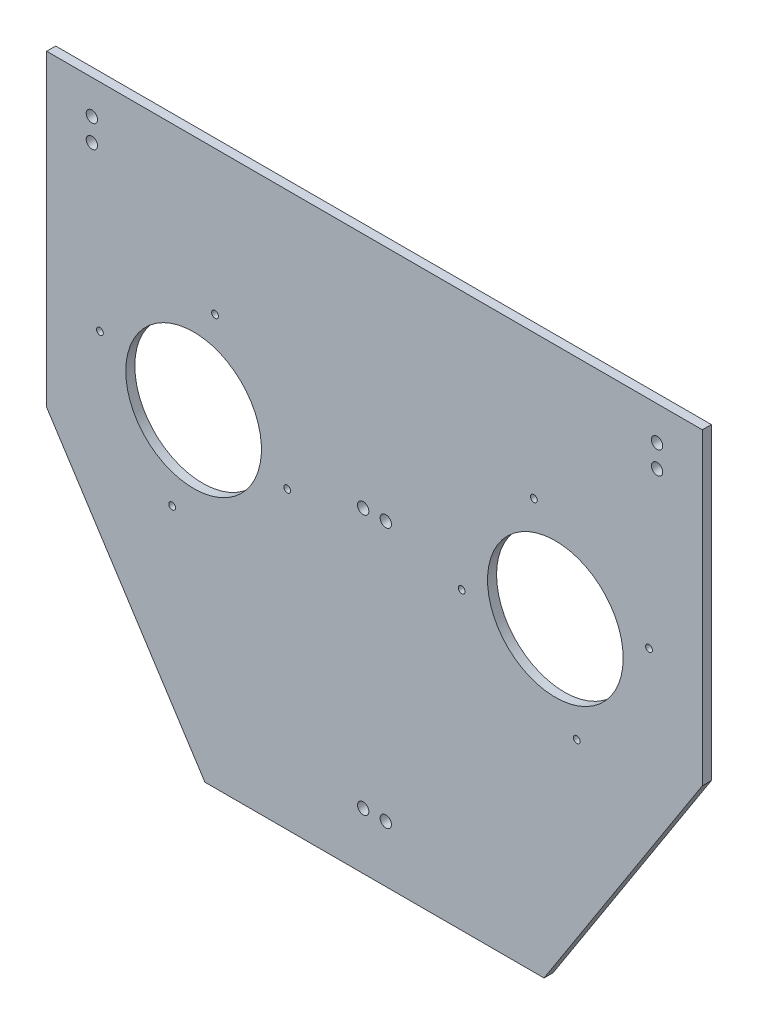
SolidWorks part; units mm, degrees
ref_plane "Front Plane" through (0, 0, 0) normal (0, 0, 1) x (1, 0, 0)
ref_plane "Top Plane" through (0, 0, 0) normal (0, 1, 0) x (1, 0, 0)
ref_plane "Right Plane" through (0, 0, 0) normal (1, 0, 0) x (0, 0, -1)
sketch "Sketch1" plane through (0, 0, 0) normal (0, 0, 1) x (1, 0, 0)
  line L0 (-125, 100) -> (125, 100) construction
  line L1 (-125, 0) -> (125, 0) construction
  line L2 (-145, -16.3871) -> (-75, -125)
  line L3 (-75, -125) -> (75, -125)
  line L4 (75, -125) -> (145, -16.3871)
  line L5 (-125, 105) -> (-125, 95) construction
  line L6 (0, -125) -> (0, 100) construction
  line L7 (-145, 120) -> (145, 120)
  line L8 (145, 120) -> (145, -16.3871)
  line L11 (-145, -16.3871) -> (-145, 120)
  line L12 (125, 105) -> (125, 95) construction
  line L13 (-5, -100) -> (5, -100) construction
  circle A0 centre (-125, 100) radius 12.5 construction
  circle A10 centre (-125, 0) radius 12.5 construction
  circle A11 centre (125, 0) radius 12.5 construction
  circle A12 centre (-125, 0) radius 17.5 construction
  circle A13 centre (-125, 100) radius 17.5 construction
  circle A25 centre (-125, 95) radius 2.5
  circle A26 centre (-125, 105) radius 2.5
  circle A27 centre (125, 95) radius 2.5
  circle A28 centre (125, 105) radius 2.5
  circle A29 centre (5, -100) radius 2.5
  circle A30 centre (-5, -100) radius 2.5
  point P12 (0, 100)
  point P15 (0, -100)
  point P45 (0, 120)
  dimension "D1" = 25
  dimension "D2" = 5
  dimension "D4" = 100
  dimension "D6" = 5
  dimension "D11" = 20
  dimension "D12" = 20
  dimension "D7" = 10
  dimension "D8" = 250
  dimension "D3" = 25
  dimension "D5" = 100
  dimension "D9" = 150
extrude "Boss-Extrude1" add sketch "Sketch1" along normal blind 4
sketch "Sketch2" plane through (0, 0, 4) normal (0, 0, 1) x (1, 0, 0)
  line L0 (121.4264, 24.4924) -> (38.5736, 5.5076) construction
  line L1 (89.4924, -26.4264) -> (70.5076, 56.4264) construction
  line L2 (0, 0) -> (0, 96.4486) construction
  line L3 (145, 120) -> (-145, 120) construction
  line L4 (-145, 120) -> (-145, -16.3871) construction
  line L5 (-80, 15) -> (80, 15) construction
  line L6 (-5, 15) -> (5, 15) construction
  circle A0 centre (80, 15) radius 42.5 construction
  circle A1 centre (38.5736, 5.5076) radius 1.5
  circle A2 centre (70.5076, 56.4264) radius 1.5
  circle A3 centre (121.4264, 24.4924) radius 1.5
  circle A4 centre (89.4924, -26.4264) radius 1.5
  circle A5 centre (80, 15) radius 30
  circle A6 centre (-38.5736, 5.5076) radius 1.5
  circle A7 centre (-70.5076, 56.4264) radius 1.5
  circle A8 centre (-89.4924, -26.4264) radius 1.5
  circle A9 centre (-121.4264, 24.4924) radius 1.5
  circle A10 centre (-80, 15) radius 42.5 construction
  circle A11 centre (-80, 15) radius 30
  circle A12 centre (-80, 15) radius 47.5 construction
  circle A15 centre (-5, 15) radius 2.5
  circle A16 centre (5, 15) radius 2.5
  point P6 (80, 15)
  point P27 (-80, 15)
  point P30 (0, 15)
  dimension "D1" = 85
  dimension "D2" = 3
  dimension "D3" = 60
  dimension "D4" = 95
  dimension "D5" = 5
  dimension "D6" = 105
  dimension "D7" = 65
  dimension "D8" = 10
extrude "Cut-Extrude1" cut sketch "Sketch2" against normal blind 10
equation "\"D1@Sketch1\" = \"cf_tube_outer_diameter\""
equation "\"mid_plate_mid_to_top\" = 100mm"
equation "\"mid_plate_mid_to_bottom\" = 100mm"
equation "\"mid_plate_horizontal_spacing\" = 250mm"
equation "\"cf_tube_outer_diameter\" = 25mm"
equation "\"D4@Sketch1\"=\"mid_plate_mid_to_top\""
equation "\"cf_tube_inner_diameter\" = 21mm"
equation "\"mid_tube_length\" = 500mm"
equation "\"cf_plate_thickness\" = 4mm"
equation "\"D1@Boss-Extrude1\"=\"cf_plate_thickness\""
equation "\"D8@Sketch1\"=\"mid_plate_horizontal_spacing\""
equation "\"D5@Sketch1\"=\"mid_plate_mid_to_bottom\""
equation "\"mid_plate_bottom_width\"= 150mm"
equation "\"D9@Sketch1\"=\"mid_plate_bottom_width\""
